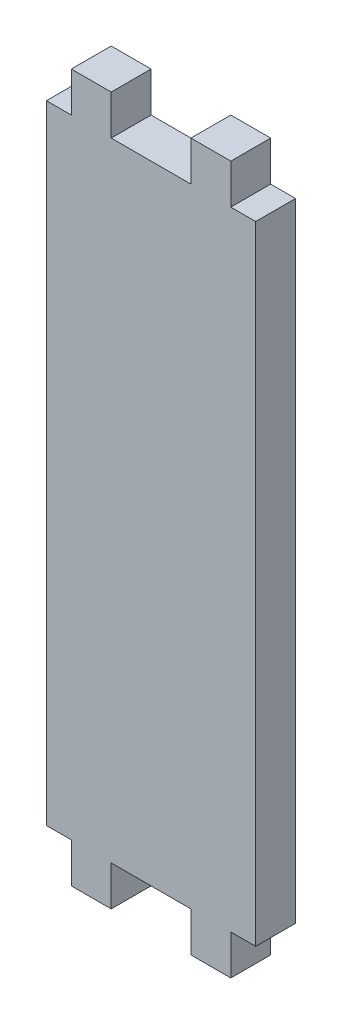
SolidWorks part; units mm, degrees
ref_plane "Front Plane" through (0, 0, 0) normal (0, 0, 1) x (1, 0, 0)
ref_plane "Top Plane" through (0, 0, 0) normal (0, 1, 0) x (1, 0, 0)
ref_plane "Right Plane" through (0, 0, 0) normal (1, 0, 0) x (0, 0, -1)
sketch "Sketch1" plane through (0, 0, 0) normal (0, 0, 1) x (1, 0, 0)
  line L1 (49.6, 34.1775) -> (76.26, 34.1775)
  line L2 (49.6, 34.1775) -> (49.6, -45.8025)
  line L3 (49.6, -45.8025) -> (76.26, -45.8025)
  line L4 (76.26, 34.1775) -> (76.26, -45.8025)
  dimension "D1" = 26.66
  dimension "D2" = 79.98
extrude "Boss-Extrude1" add sketch "Sketch1" along normal blind 5.08
sketch "Sketch3" plane through (0, 0, 5.08) normal (0, 0, 1) x (1, 0, 0)
  line L0 (62.93, 34.1775) -> (62.93, -45.8025) construction
  line L1 (76.26, 34.1775) -> (49.6, 34.1775) construction
  line L2 (49.6, -45.8025) -> (76.26, -45.8025) construction
  line L3 (49.6, -5.8125) -> (76.26, -5.8125) construction
  line L4 (49.6, 34.1775) -> (49.6, -45.8025) construction
  line L5 (76.26, -45.8025) -> (76.26, 34.1775) construction
  line L6 (52.77, -45.8025) -> (52.77, -50.8825)
  line L7 (68.01, 34.1775) -> (73.09, 34.1775)
  line L8 (68.01, 34.1775) -> (68.01, 39.2575)
  line L9 (68.01, 39.2575) -> (73.09, 39.2575)
  line L10 (73.09, 34.1775) -> (73.09, 39.2575)
  line L11 (57.85, 34.1775) -> (52.77, 34.1775)
  line L12 (57.85, 34.1775) -> (57.85, 39.2575)
  line L13 (57.85, 39.2575) -> (52.77, 39.2575)
  line L14 (52.77, 34.1775) -> (52.77, 39.2575)
  line L15 (57.85, -50.8825) -> (52.77, -50.8825)
  line L16 (57.85, -45.8025) -> (57.85, -50.8825)
  line L17 (57.85, -45.8025) -> (52.77, -45.8025)
  line L18 (73.09, -45.8025) -> (73.09, -50.8825)
  line L19 (68.01, -50.8825) -> (73.09, -50.8825)
  line L20 (68.01, -45.8025) -> (68.01, -50.8825)
  line L21 (68.01, -45.8025) -> (73.09, -45.8025)
  dimension "D1" = 5.08
  dimension "D2" = 5.08
  dimension "D3" = 5.08
  dimension "D4" = 5.08
  dimension "D5" = 5.08
  dimension "D6" = 5.08
extrude "Boss-Extrude2" add sketch "Sketch3" against normal blind 5.08
sketch "Sketch4" plane through (0, 0, 5.08) normal (0, 0, 1) x (1, 0, 0)
  line L0 (49.6, 7.5175) -> (76.26, 7.5175)
  line L1 (49.6, 34.1775) -> (49.6, -45.8025) construction
  line L2 (76.26, -45.8025) -> (76.26, 34.1775) construction
  line L3 (76.26, -19.1425) -> (49.6, -19.1425)
  line L4 (57.85, -45.8025) -> (68.01, -45.8025) construction
  dimension "D1" = 26.66
  dimension "D2" = 26.66
